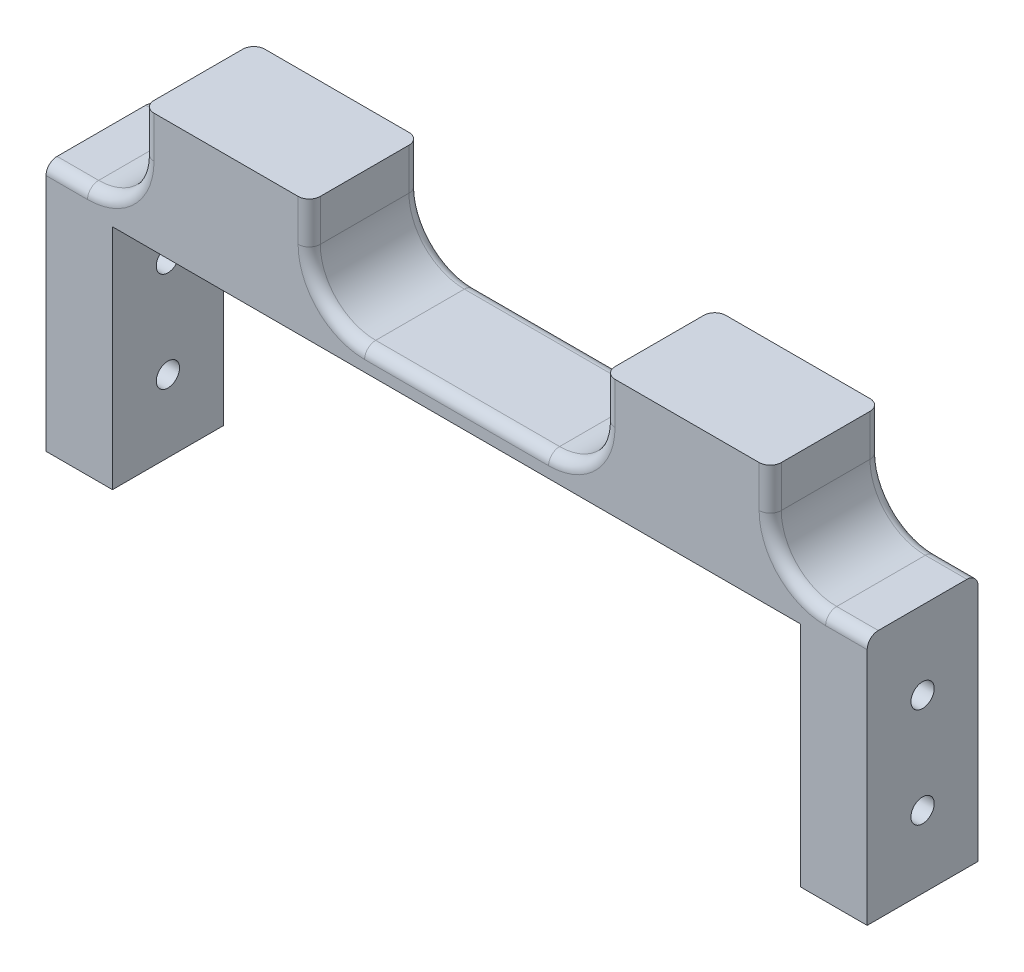
SolidWorks part; units mm, degrees
material "ABS"
ref_plane "Front Plane" through (0, 0, 0) normal (0, 0, 1) x (1, 0, 0)
ref_plane "Top Plane" through (0, 0, 0) normal (0, 1, 0) x (1, 0, 0)
ref_plane "Right Plane" through (0, 0, 0) normal (1, 0, 0) x (0, 0, -1)
sketch "Sketch1" plane through (0, 0, 0) normal (0, 0, 1) x (1, 0, 0)
  line L0 (62.1, -20.55) -> (74.1, -20.55)
  line L1 (-62.1, -20.55) -> (62.1, -20.55)
  line L2 (-62.1, -20.55) -> (-62.1, 20.55)
  line L3 (-62.1, 20.55) -> (62.1, 20.55)
  line L4 (62.1, -20.55) -> (62.1, 20.55)
  line L5 (-62.1, -20.55) -> (62.1, 20.55) construction
  line L6 (-62.1, 20.55) -> (62.1, -20.55) construction
  line L7 (74.1, -20.55) -> (74.1, 24.55)
  line L8 (74.1, 24.55) -> (-74.1, 24.55)
  line L9 (-74.1, 24.55) -> (-74.1, -20.55)
  line L10 (-74.1, -20.55) -> (-62.1, -20.55)
  point P0 (0, 0)
  dimension "D1" = 124.2
  dimension "D2" = 41.1
  dimension "D3" = 12
  dimension "D5" = 4
extrude "Boss-Extrude1" add sketch "Sketch1" along normal blind 20 contours L9 L10 L2 L3 L4 L0 L7 L8 region at (63.6491, 0, 0)
sketch "Sketch2" plane through (-74.1, 0, 0) normal (-1, 0, 0) x (0, 0, 1)
  line L0 (20, -20.55) -> (0, -20.55) construction
  line L3 (0, 24.55) -> (0, -20.55) construction
  circle A0 centre (10, 10.45) radius 2.1
  circle A1 centre (10, -7.55) radius 2.1
  point P8 (0, 0)
  dimension "D1" = 4.2
  dimension "D2" = 18
  dimension "D3" = 13
  dimension "D4" = 10
extrude "Cut-Extrude1" cut sketch "Sketch2" against normal blind 149
sketch "Sketch3" plane through (0, 0, 20) normal (0, 0, 1) x (1, 0, 0)
  line L0 (-56.6, 24.55) -> (-56.6, 42.05)
  line L1 (74.1, 24.55) -> (-74.1, 24.55) construction
  line L2 (-56.6, 42.05) -> (-26.6, 42.05)
  line L3 (-26.6, 42.05) -> (-26.6, 24.55)
  line L4 (-26.6, 24.55) -> (-56.6, 24.55)
  line L5 (-74.1, 24.55) -> (-74.1, -20.55) construction
  dimension "D1" = 17.5
  dimension "D2" = 30
  dimension "D3" = 17.5
extrude "Boss-Extrude2" add sketch "Sketch3" against normal blind 20
fillet "Fillet1" radius 10 2 edges at (-26.6, 24.55, 10) (-56.6, 24.55, 10)
ref_plane "Plane1" through (0, 0, 0) normal (1, 0, 0) x (0, 0, -1)
mirror "Mirror1" about plane through (0, 0, 0) normal (1, 0, 0) of "Fillet1", "Boss-Extrude2"
fillet "Fillet2" radius 2 22 edges at (-56.6, 38.3, 0) (-59.5289, 27.4789, 0) (26.6, 38.3, 0) (23.6711, 27.4789, 0) (-26.6, 38.3, 0) (-23.6711, 27.4789, 0) (56.6, 38.3, 0) (70.35, 24.55, 0) (70.35, 24.55, 20) (56.6, 38.3, 20) (26.6, 38.3, 20) (23.6711, 27.4789, 20) (0, 24.55, 20) (-26.6, 38.3, 20) (-56.6, 38.3, 20) (-70.35, 24.55, 20) (-70.35, 24.55, 0) (0, 24.55, 0) (59.5289, 27.4789, 0) (59.5289, 27.4789, 20) (-23.6711, 27.4789, 20) (-59.5289, 27.4789, 20)
